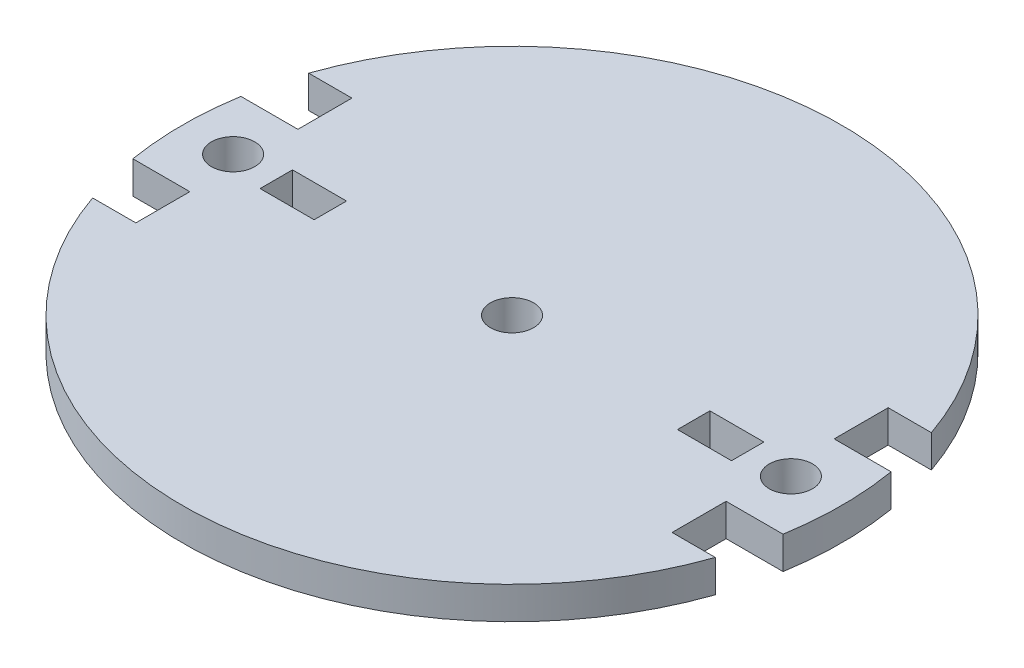
SolidWorks part; units mm, degrees
ref_plane "Alzado" through (0, 0, 0) normal (0, 0, 1) x (1, 0, 0)
ref_plane "Planta" through (0, 0, 0) normal (0, 1, 0) x (1, 0, 0)
ref_plane "Vista lateral" through (0, 0, 0) normal (1, 0, 0) x (0, 0, -1)
sketch "Croquis1" plane through (0, 0, 0) normal (0, 1, 0) x (1, 0, 0)
  circle A0 centre (0, 0) radius 30.5
extrude "Saliente-Extruir1" add sketch "Croquis1" along normal blind 3
sketch "Croquis2" plane through (0, 3, 0) normal (0, 1, 0) x (1, 0, 0)
  circle A0 centre (0, 0) radius 2
extrude "Cortar-Extruir1" cut sketch "Croquis2" against normal blind 4
sketch "Croquis5" plane through (0, 3, 0) normal (0, 1, 0) x (1, 0, 0)
  line L0 (0, 0) -> (0, 10)
  line L1 (28.8141, -5) -> (30.0874, -5)
  line L2 (28.8141, 5) -> (30.0874, 5)
  line L3 (-24.8141, 10) -> (-28.8141, 10)
  line L4 (24.8141, -5) -> (24.8141, -10)
  line L5 (-24.8141, -10) -> (-28.8141, -10)
  line L6 (24.8141, -5) -> (28.8141, -5)
  line L7 (24.8141, 5) -> (24.8141, 10)
  line L8 (-24.8141, 5) -> (-28.8141, 5)
  line L9 (-24.8141, 5) -> (-24.8141, 10)
  line L10 (-24.8141, -5) -> (-28.8141, -5)
  line L11 (-24.8141, -5) -> (-24.8141, -10)
  line L12 (24.8141, 5) -> (28.8141, 5)
  line L13 (24.8141, -10) -> (28.8141, -10)
  line L14 (24.8141, 10) -> (28.8141, 10)
  line L15 (-28.8141, 5) -> (-30.0874, 5)
  line L16 (-28.8141, -5) -> (-30.0874, -5)
  circle A1 centre (0, 0) radius 30.5 construction
  arc A2 (-28.8141, 10) -> (-30.0874, 5) centre (0, 0) ccw
  arc A3 (28.8141, 10) -> (28.8141, -10) centre (0, 0) cw
  arc A4 (-30.0874, -5) -> (-28.8141, -10) centre (0, 0) ccw
  arc A5 (30.0874, -5) -> (28.8141, -10) centre (0, 0) cw
  arc A6 (28.8141, 10) -> (30.0874, 5) centre (0, 0) cw
  circle M2 centre (0, 0) radius 30.5
extrude "Cortar-Extruir3" cut sketch "Croquis5" against normal blind 4 contours L11 L10 L8 L9 L3 L5 M2 | L15 L8 L9 L3 M2 | L14 L7 L12 L2 M2 | L4 L13 L1 L6 M2 region at (27.1844, 3, 7.3876) region at (27.1844, 3, -7.3876) region at (-27.1844, 3, 7.3876) region at (-27.1844, 3, -7.3876)
sketch "Croquis6" plane through (0, 3, 0) normal (0, 1, 0) x (1, 0, 0)
  line L0 (16.8141, 1.5) -> (21.8141, 1.5)
  line L1 (-16.8141, 1.5) -> (-16.8141, -1.5)
  line L2 (-16.8141, -1.5) -> (-21.8141, -1.5)
  line L3 (-21.8141, -1.5) -> (-21.8141, 1.5)
  line L5 (-16.8141, 1.5) -> (-21.8141, 1.5)
  line L6 (21.8141, -1.5) -> (21.8141, 1.5)
  line L7 (16.8141, -1.5) -> (21.8141, -1.5)
  line L8 (16.8141, 1.5) -> (16.8141, -1.5)
extrude "Cortar-Extruir4" cut sketch "Croquis6" against normal blind 4
sketch "Croquis7" plane through (0, 3, 0) normal (0, 1, 0) x (1, 0, 0)
  circle A1 centre (-25.8141, 0) radius 2
  circle A2 centre (25.8141, 0) radius 2
extrude "Cortar-Extruir5" cut sketch "Croquis7" against normal blind 4
